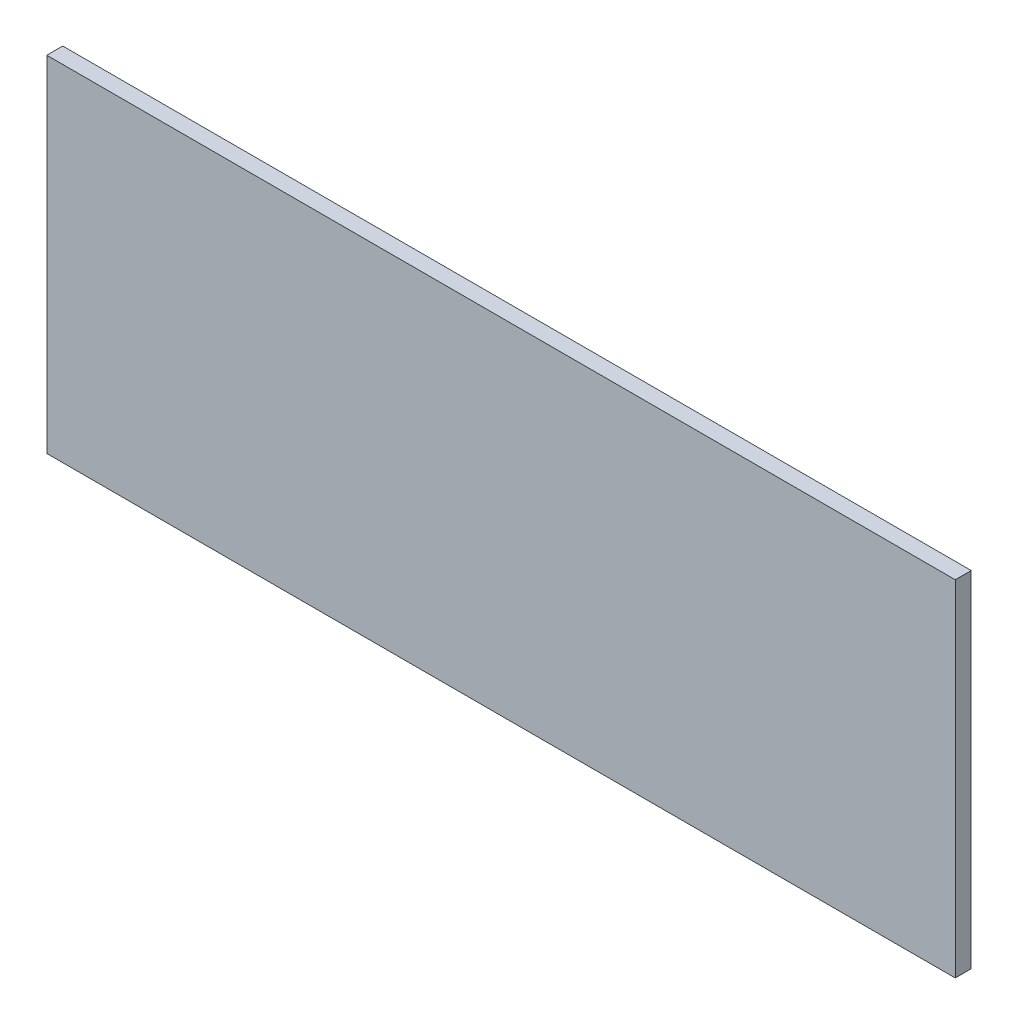
SolidWorks part; units mm, degrees
ref_plane "Front Plane" through (0, 0, 0) normal (0, 0, 1) x (1, 0, 0)
ref_plane "Top Plane" through (0, 0, 0) normal (0, 1, 0) x (1, 0, 0)
ref_plane "Right Plane" through (0, 0, 0) normal (1, 0, 0) x (0, 0, -1)
sketch "Sketch1" plane through (0, 0, 0) normal (0, 0, 1) x (1, 0, 0)
  line L1 (-49.9407, 51.4574) -> (58.0593, 51.4574)
  line L2 (-49.9407, 51.4574) -> (-49.9407, 10.4574)
  line L3 (-49.9407, 10.4574) -> (58.0593, 10.4574)
  line L4 (58.0593, 51.4574) -> (58.0593, 10.4574)
  dimension "D1" = 108
  dimension "D2" = 41
base flange "Base-Flange1" sketch "Sketch1" thickness 1.8974 reverse thickness direction no parameters "D1"=2.54
sketch "Bend-Lines1" plane through (0, 0, 0) normal (0, 1, 0) x (1, 0, 0)
sketch "Bounding-Box1" plane through (0, 0, 0) normal (0, 1, 0) x (1, 0, 0)
sheet metal parameters "Sheet-Metal1" thickness 1.8974 parameters "D1"=2.54
flat pattern "Flat-Pattern1" [suppressed]
sketch "Bend-Lines2" plane through (0, 0, 0) normal (0, 1, 0) x (1, 0, 0)
sketch "Bounding-Box2" [suppressed] plane through (0, 0, 0) normal (0, 1, 0) x (1, 0, 0)
